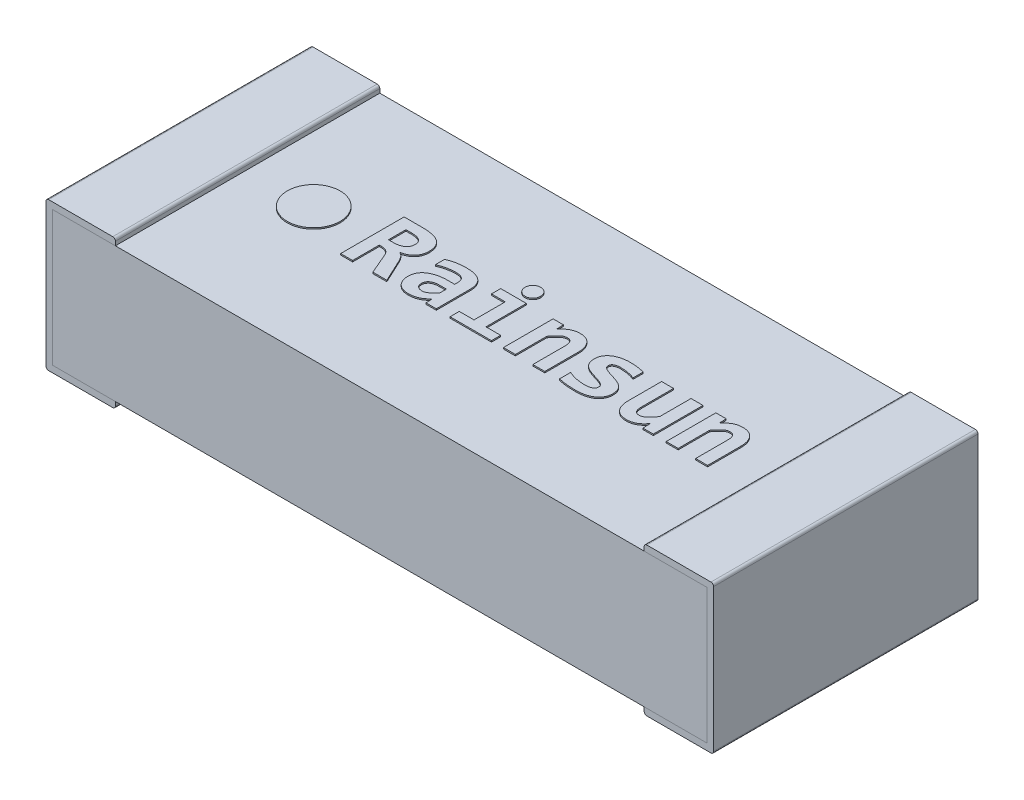
SolidWorks part; units mm, degrees
ref_plane "Front Plane" through (0, 0, 0) normal (0, 0, 1) x (1, 0, 0)
ref_plane "Top Plane" through (0, 0, 0) normal (0, 1, 0) x (1, 0, 0)
ref_plane "Right Plane" through (0, 0, 0) normal (1, 0, 0) x (0, 0, -1)
sketch "Sketch1" plane through (0, 0, 0) normal (0, 0, 1) x (1, 0, 0)
  line L0 (0, 0) -> (2.525, 0) construction
  line L1 (2.525, 0) -> (2.525, 0.05) construction
  line L2 (2.525, 0.05) -> (2.475, 0.05) construction
  line L3 (2.475, 0.05) -> (2, 0.05)
  line L4 (2.475, 0.05) -> (2.475, 1.07)
  line L5 (2.475, 1.07) -> (2, 1.07)
  dimension "D1" = 0.05
  dimension "D2" = 0.475
  dimension "D3" = 1.02
  dimension "D4" = 2.525
extrude "Extrude-Thin1" add sketch "Sketch1" along normal blind 1 and the other way blind 1 thin thin type one direction wall 0.05
mirror "Mirror1" about plane through (0, 0, 0) normal (1, 0, 0) of bodies 101
sketch "Sketch2" plane through (0, 0, 0) normal (0, 0, 1) x (1, 0, 0)
  line L1 (-2.475, 0.05) -> (2.475, 0.05)
  line L2 (-2.475, 0.05) -> (-2.475, 1.07)
  line L3 (-2.475, 1.07) -> (2.475, 1.07)
  line L4 (2.475, 0.05) -> (2.475, 1.07)
extrude "Boss-Extrude1" add sketch "Sketch2" along normal blind 1 and the other way blind 1 separate body
sketch "Sketch3" plane through (0, 1.07, 0) normal (0, 1, 0) x (1, 0, 0)
  line L0 (0, 0) -> (-1.5, 0) construction
  circle A0 centre (-1.5, 0) radius 0.2
  text T0 "Rainsun" font "Consolas" height 0.48
  point P5 (-3, 0)
  dimension "D1" = 0.4
  dimension "D2" = 1.5
extrude "Boss-Extrude2" add sketch "Sketch3" along normal blind 0.01 separate body
fillet "Fillet1" radius 0.02 4 edges at (2.525, 0, 0) (2.525, 1.12, 0) (2, 0, 0) (2, 1.12, 0)
fillet "Fillet2" radius 0.02 4 edges at (-2.525, 0, 0) (-2.525, 1.12, 0) (-2, 1.12, 0) (-2, 0, 0)
equation "\"A\" = 5.05mm"
equation "\"B\" = 2.0mm"
equation "\"C\" = 0.5mm"
equation "\"H\"= 1.07mm"
equation "\"ElectrodeThickness\"= 0.05mm"
equation "\"D1@Sketch1\"=\"ElectrodeThickness\"'/2"
equation "\"D2@Sketch1\"=\"C\"-\"ElectrodeThickness\"/2"
equation "\"D3@Sketch1\"=\"H\"-\"ElectrodeThickness\""
equation "\"D5@Extrude-Thin1\"=\"ElectrodeThickness\""
equation "\"D1@Extrude-Thin1\"=\"B\"/2"
equation "\"D2@Extrude-Thin1\"=\"B\"/2"
equation "\"D1@Boss-Extrude1\"=\"B\"/2"
equation "\"D2@Boss-Extrude1\"=\"B\"/2"
equation "\"D4@Sketch1\"=\"A\"/2"
